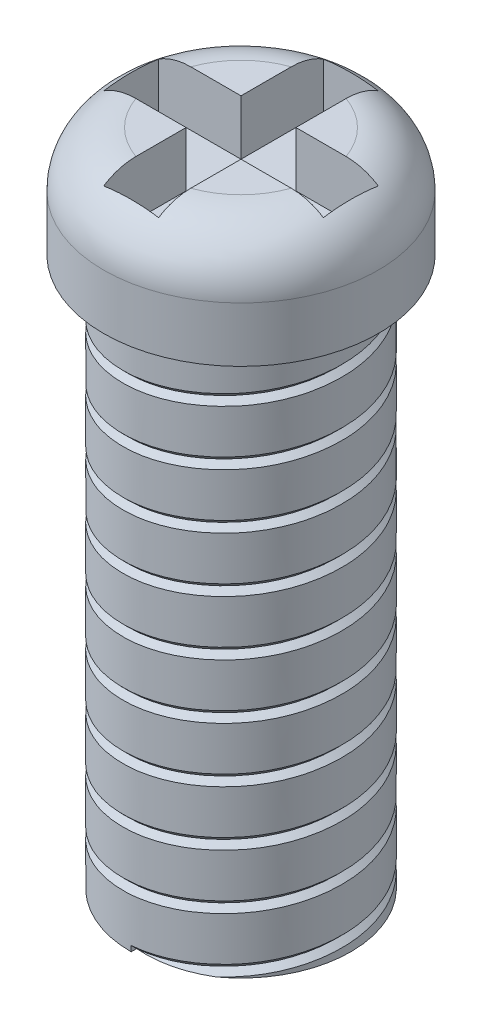
SolidWorks part; units mm, degrees
ref_plane "Alzado" through (0, 0, 0) normal (0, 0, 1) x (1, 0, 0)
ref_plane "Planta" through (0, 0, 0) normal (0, 1, 0) x (1, 0, 0)
ref_plane "Vista lateral" through (0, 0, 0) normal (1, 0, 0) x (0, 0, -1)
sketch "Croquis2" plane through (0, 0, 0) normal (0, 1, 0) x (1, 0, 0)
  circle A0 centre (0, 0) radius 2.5
  point P3 (0, 0)
extrude "Saliente-Extruir1" add sketch "Croquis2" along normal blind 12
sketch "Croquis3" plane through (0, 0, 0) normal (0, -1, 0) x (1, 0, 0)
  circle A0 centre (0, 0) radius 2
  circle A1 centre (0, 0) radius 2.5
extrude "Cortar-Extruir2" cut sketch "Croquis3" against normal blind 10
sketch "Croquis5" plane through (0, 0, 0) normal (0, -1, 0) x (1, 0, 0)
  circle A0 centre (0, 0) radius 1.9
curve "Hélice/Espiral2" pitch 1 height 10 radius 1.9 centre (0, 0, 0) axis (0, 1, 0) start towards (0, 0, -1)
sketch "Croquis6" plane through (0, 0, 0) normal (1, 0, 0) x (0, 0, -1)
  line L0 (-1.9, 0) -> (-2.1234, 0.2234)
  line L1 (-2.1234, 0.2234) -> (-2.1234, -0.2234)
  line L2 (-2.1234, -0.2234) -> (-1.9, 0)
  spline S0 degree 3 poles (-1.9, 0) (-1.9, 0.0207) (-1.8011, 0.0626) (-1.3785, 0.125) (-0.746, 0.1875) (0, 0.25) (0.746, 0.3125) (1.3785, 0.375) (1.8011, 0.4375) (1.9495, 0.5) (1.8011, 0.5625) (1.3785, 0.625) (0.746, 0.6875) (0, 0.75) (-0.746, 0.8125) (-1.3785, 0.875) (-1.8011, 0.9375) (-1.9495, 1) (-1.8011, 1.0625) (-1.3785, 1.125) (-0.746, 1.1875) (0, 1.25) (0.746, 1.3125) (1.3785, 1.375) (1.8011, 1.4375) (1.9495, 1.5) (1.8011, 1.5625) (1.3785, 1.625) (0.746, 1.6875) (0, 1.75) (-0.746, 1.8125) (-1.3785, 1.875) (-1.8011, 1.9375) (-1.9495, 2) (-1.8011, 2.0625) (-1.3785, 2.125) (-0.746, 2.1875) (0, 2.25) (0.746, 2.3125) (1.3785, 2.375) (1.8011, 2.4375) (1.9495, 2.5) (1.8011, 2.5625) (1.3785, 2.625) (0.746, 2.6875) (0, 2.75) (-0.746, 2.8125) (-1.3785, 2.875) (-1.8011, 2.9375) (-1.9495, 3) (-1.8011, 3.0625) (-1.3785, 3.125) (-0.746, 3.1875) (0, 3.25) (0.746, 3.3125) (1.3785, 3.375) (1.8011, 3.4375) (1.9495, 3.5) (1.8011, 3.5625) (1.3785, 3.625) (0.746, 3.6875) (0, 3.75) (-0.746, 3.8125) (-1.3785, 3.875) (-1.8011, 3.9375) (-1.9495, 4) (-1.8011, 4.0625) (-1.3785, 4.125) (-0.746, 4.1875) (0, 4.25) (0.746, 4.3125) (1.3785, 4.375) (1.8011, 4.4375) (1.9495, 4.5) (1.8011, 4.5625) (1.3785, 4.625) (0.746, 4.6875) (0, 4.75) (-0.746, 4.8125) (-1.3785, 4.875) (-1.8011, 4.9375) (-1.9495, 5) (-1.8011, 5.0625) (-1.3785, 5.125) (-0.746, 5.1875) (0, 5.25) (0.746, 5.3125) (1.3785, 5.375) (1.8011, 5.4375) (1.9495, 5.5) (1.8011, 5.5625) (1.3785, 5.625) (0.746, 5.6875) (0, 5.75) (-0.746, 5.8125) (-1.3785, 5.875) (-1.8011, 5.9375) (-1.9495, 6) (-1.8011, 6.0625) (-1.3785, 6.125) (-0.746, 6.1875) (0, 6.25) (0.746, 6.3125) (1.3785, 6.375) (1.8011, 6.4375) (1.9495, 6.5) (1.8011, 6.5625) (1.3785, 6.625) (0.746, 6.6875) (0, 6.75) (-0.746, 6.8125) (-1.3785, 6.875) (-1.8011, 6.9375) (-1.9495, 7) (-1.8011, 7.0625) (-1.3785, 7.125) (-0.746, 7.1875) (0, 7.25) (0.746, 7.3125) (1.3785, 7.375) (1.8011, 7.4375) (1.9495, 7.5) (1.8011, 7.5625) (1.3785, 7.625) (0.746, 7.6875) (0, 7.75) (-0.746, 7.8125) (-1.3785, 7.875) (-1.8011, 7.9375) (-1.9495, 8) (-1.8011, 8.0625) (-1.3785, 8.125) (-0.746, 8.1875) (0, 8.25) (0.746, 8.3125) (1.3785, 8.375) (1.8011, 8.4375) (1.9495, 8.5) (1.8011, 8.5625) (1.3785, 8.625) (0.746, 8.6875) (0, 8.75) (-0.746, 8.8125) (-1.3785, 8.875) (-1.8011, 8.9375) (-1.9495, 9) (-1.8011, 9.0625) (-1.3785, 9.125) (-0.746, 9.1875) (0, 9.25) (0.746, 9.3125) (1.3785, 9.375) (1.8011, 9.4375) (1.9495, 9.5) (1.8011, 9.5625) (1.3785, 9.625) (0.746, 9.6875) (0, 9.75) (-0.746, 9.8125) (-1.3785, 9.875) (-1.8011, 9.9374) (-1.9, 9.9793) (-1.9, 10) knots 0 0 0 0 0.00625 0.0125 0.01875 0.025 0.03125 0.0375 0.04375 0.05 0.05625 0.0625 0.06875 0.075 0.08125 0.0875 0.09375 0.1 0.10625 0.1125 0.11875 0.125 0.13125 0.1375 0.14375 0.15 0.15625 0.1625 0.16875 0.175 0.18125 0.1875 0.19375 0.2 0.20625 0.2125 0.21875 0.225 0.23125 0.2375 0.24375 0.25 0.25625 0.2625 0.26875 0.275 0.28125 0.2875 0.29375 0.3 0.30625 0.3125 0.31875 0.325 0.33125 0.3375 0.34375 0.35 0.35625 0.3625 0.36875 0.375 0.38125 0.3875 0.39375 0.4 0.40625 0.4125 0.41875 0.425 0.43125 0.4375 0.44375 0.45 0.45625 0.4625 0.46875 0.475 0.48125 0.4875 0.49375 0.5 0.50625 0.5125 0.51875 0.525 0.53125 0.5375 0.54375 0.55 0.55625 0.5625 0.56875 0.575 0.58125 0.5875 0.59375 0.6 0.60625 0.6125 0.61875 0.625 0.63125 0.6375 0.64375 0.65 0.65625 0.6625 0.66875 0.675 0.68125 0.6875 0.69375 0.7 0.70625 0.7125 0.71875 0.725 0.73125 0.7375 0.74375 0.75 0.75625 0.7625 0.76875 0.775 0.78125 0.7875 0.79375 0.8 0.80625 0.8125 0.81875 0.825 0.83125 0.8375 0.84375 0.85 0.85625 0.8625 0.86875 0.875 0.88125 0.8875 0.89375 0.9 0.90625 0.9125 0.91875 0.925 0.93125 0.9375 0.94375 0.95 0.95625 0.9625 0.96875 0.975 0.98125 0.9875 0.99375 1 1 1 1 construction
sweep "Cortar-Barrer1" cut profiles "Croquis6" path "Hélice/Espiral2"
fillet "Redondeo4" radius 1 1 edges at (0, 12, 2.5)
sketch "Croquis7" plane through (0, 12, 0) normal (0, 1, 0) x (1, 0, 0)
  line L1 (2, -0.5) -> (-2, -0.5)
  line L2 (2, -0.5) -> (2, 0.5)
  line L3 (2, 0.5) -> (-2, 0.5)
  line L4 (-2, -0.5) -> (-2, 0.5)
  line L5 (2, -0.5) -> (-2, 0.5) construction
  line L6 (2, 0.5) -> (-2, -0.5) construction
  line L7 (0.5, -2) -> (-0.5, -2)
  line L8 (0.5, -2) -> (0.5, 2)
  line L9 (0.5, 2) -> (-0.5, 2)
  line L10 (-0.5, -2) -> (-0.5, 2)
  line L11 (0.5, -2) -> (-0.5, 2) construction
  line L12 (0.5, 2) -> (-0.5, -2) construction
  point P0 (0, 0)
  point P5 (0, 0)
extrude "Cortar-Extruir3" cut sketch "Croquis7" against normal blind 1 contours L4 L3 L2 L1 | L10 L9 L8 L7
